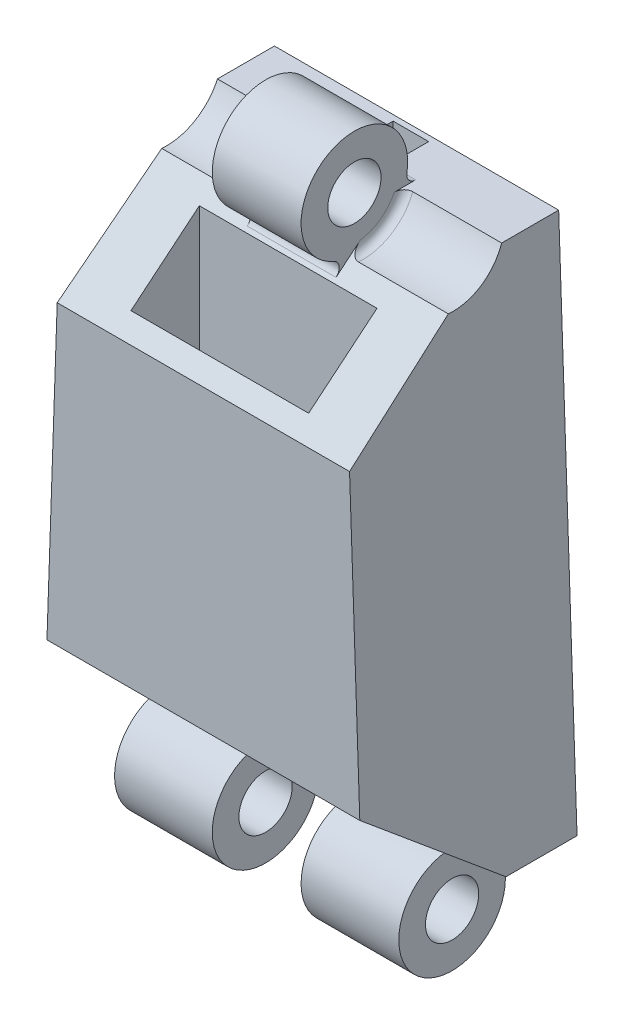
SolidWorks part; units mm, degrees
ref_plane "Front Plane" through (0, 0, 0) normal (0, 0, 1) x (1, 0, 0)
ref_plane "Top Plane" through (0, 0, 0) normal (0, 1, 0) x (1, 0, 0)
ref_plane "Right Plane" through (0, 0, 0) normal (1, 0, 0) x (0, 0, -1)
sketch "Sketch1" plane through (0, 0, 0) normal (0, 0, 1) x (1, 0, 0)
  line L0 (-8, -14.5) -> (-6.9661, 15.4822)
  line L3 (-8, -14.5) -> (10.0677, -14.5)
  line L5 (10.0677, -14.5) -> (9.0339, 15.4822)
  line L6 (-6.9661, 15.4822) -> (9.0339, 15.4822)
  point P0 (0, 0)
extrude "Boss-Extrude2" add sketch "Sketch1" along normal blind 12
sketch "Sketch15" plane through (0, 0, 0) normal (0, 0, -1) x (-1, 0, 0)
  line L0 (6.9661, 15.4822) -> (-9.0339, 15.4822)
  line L1 (-1.0339, 15.4822) -> (-1.0339, 5.488)
ref_plane "Plane1" through (1.0339, 0, 0) normal (1, 0, 0) x (0, 0, -1)
sketch "Sketch16" plane through (1.0339, 0, 0) normal (1, 0, 0) x (0, 0, -1)
  line L0 (0, 15.4822) -> (-4, 15.4822)
  line L6 (-12, 15.4822) -> (0, 15.4822) construction
  line L7 (-4, 15.4822) -> (-12, 8.8525)
  line L8 (-12, -14.5) -> (-12, 15.4822) construction
  line L9 (-12, 8.8525) -> (-12, 15.4822)
  line L10 (-12, 15.4822) -> (-4, 15.4822)
extrude "Cut-Extrude2" cut sketch "Sketch16" against normal through all both and the other way through all contours L10 L9 L7 region at (1.0339, 13.2723, 9.3333)
sketch "Sketch17" plane through (1.0339, 0, 0) normal (1, 0, 0) x (0, 0, -1)
  line L0 (-12, 8.8525) -> (-12, 18.723)
  line L1 (0, 15.4822) -> (-12, 15.4822)
  line L2 (-6, 15.4822) -> (-6, 16.5822)
  circle A0 centre (-6, 16.5822) radius 1.5
  circle A1 centre (-6, 16.5822) radius 3
extrude "Boss-Extrude3" add sketch "Sketch17" along normal mid plane 5 contours L1 A1 A0 | L1 A1 A0 region at (1.0339, 14.6478, 6) region at (1.0339, 15.5549, 4.0946)
sketch "Sketch18" plane through (1.0339, 0, 0) normal (1, 0, 0) x (0, 0, -1)
  line L0 (0, -14.5) -> (-4, -14.5)
  line L1 (-12, -14.5) -> (0, -14.5) construction
  line L2 (-4, -14.5) -> (-12, -7.8704)
  line L3 (-12, -14.5) -> (-12, 8.8525) construction
  line L4 (-12, -7.8704) -> (-12, -14.5)
  line L5 (-12, -14.5) -> (-4, -14.5)
extrude "Cut-Extrude3" cut sketch "Sketch18" against normal through all both and the other way through all contours L4 L5 L2 region at (1.0339, -12.2901, 9.3333)
sketch "Sketch19" plane through (1.0339, 0, 0) normal (1, 0, 0) x (0, 0, -1)
  line L0 (-12, -7.8704) -> (-12, -19.6668)
  line L1 (0, -14.5) -> (-3.2089, -14.5)
  line L3 (-8.7911, -14.5) -> (-12, -14.5)
  circle A0 centre (-6, -15.6) radius 1.5
  circle A1 centre (-6, -15.6) radius 3
extrude "Boss-Extrude4" add sketch "Sketch19" along normal mid plane 16 contours A1 A0 region at (1.0339, -18.4639, 6.544)
extrude "Cut-Extrude4" cut sketch "Sketch19<3>" against normal mid plane 5 contours A1
sketch "Sketch19<3>" plane through (1.0339, 0, 0) normal (1, 0, 0) x (0, 0, -1) same geometry as "Sketch19"
sketch "Sketch20" plane through (3.5339, 0, 0) normal (1, 0, 0) x (0, 0, -1)
  circle A0 centre (-6, 16.5822) radius 3
extrude "Cut-Extrude5" cut sketch "Sketch20" along normal blind 10
sketch "Sketch21" plane through (-1.4661, 0, 0) normal (-1, 0, 0) x (0, 0, 1)
  circle A0 centre (6, 16.5822) radius 3
extrude "Cut-Extrude6" cut sketch "Sketch21" along normal blind 10
fillet "Fillet6" radius 0.5 1 edges at (1.0339, 13.595, 6.2772)
fillet "Fillet7" radius 0.5 1 edges at (1.0339, 15.4822, 3.2089)
fillet "Fillet8" radius 0.5 2 edges at (3.5339, 14.0268, 4.4283) (-1.4661, 14.0268, 4.4283)
sketch "Sketch22" plane through (0, 11.1439, 9.235) normal (0, 0.77, 0.6381) x (1, 0, 0)
  line L0 (1.0339, -3.591) -> (1.0339, -2.391)
  line L1 (-7.1947, -3.591) -> (9.2625, -3.591) construction
  line L2 (-3.9661, -2.391) -> (6.0339, -2.391)
  line L3 (6.0339, -2.391) -> (6.0339, 2.609)
  line L4 (6.0339, 2.609) -> (-3.9661, 2.609)
  line L5 (-3.9661, 2.609) -> (-3.9661, -2.391)
  point P7 (1.0339, -2.391)
sketch "Sketch23" plane through (0, 0, 0) normal (0, 1, 0) x (1, 0, 0)
  line L0 (-3.9661, -7.2262) -> (-3.9661, -11.076)
  line L1 (-3.9661, -11.076) -> (6.0339, -11.076)
  line L2 (6.0339, -11.076) -> (6.0339, -7.2262)
  line L3 (6.0339, -7.2262) -> (-3.9661, -7.2262)
extrude "Cut-Extrude7" cut sketch "Sketch23" against normal up to surface and the other way up to surface up to face at (1.0339, -12.4192, 6.5109) other way up to face at (1.0451, 12.5917, 7.4879)
sketch "Sketch24" plane through (1.0339, 0, 0) normal (1, 0, 0) x (0, 0, -1)
  line L0 (-0.32, -14.5) -> (-2.32, -14.5)
  line L1 (-4, -14.5) -> (0, -14.5) construction
  line L2 (-2.32, -14.5) -> (-2.32, -13.4312)
  line L4 (-0.32, -13.4312) -> (-0.32, 17.7135)
  line L5 (-0.32, 17.7135) -> (-2.32, 17.7135)
  line L6 (-2.32, 17.7135) -> (-2.32, -13.4312)
  line L7 (-0.32, -13.4312) -> (-0.32, -14.5)
extrude "Cut-Extrude8" cut sketch "Sketch24" against normal mid plane 2
